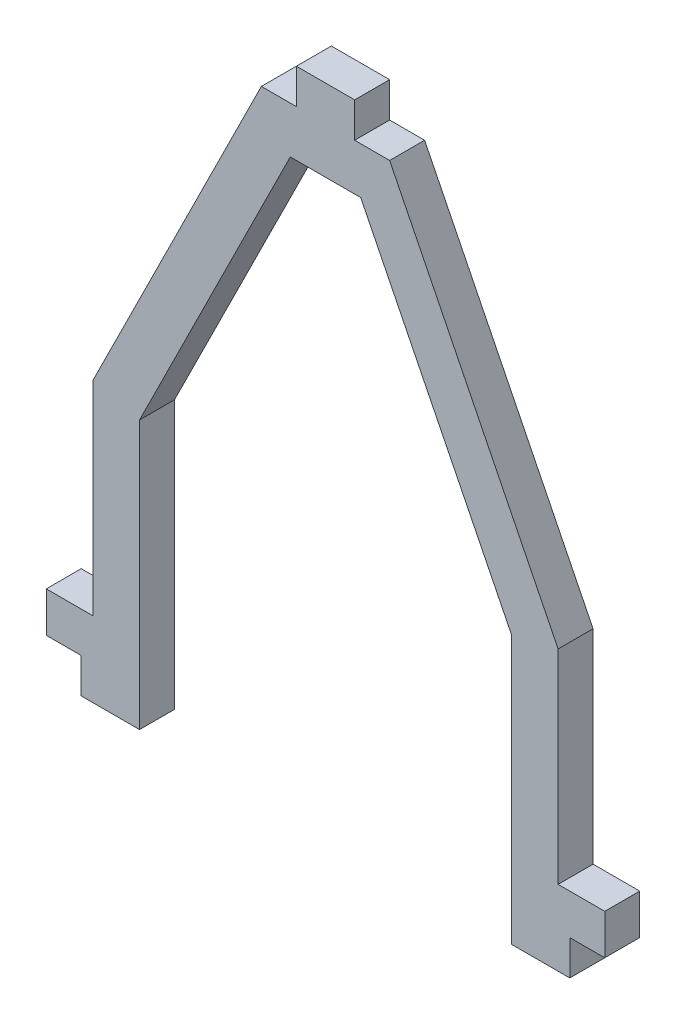
SolidWorks part; units mm, degrees
material "Custom Plastic"
ref_plane "Front Plane" through (0, 0, 0) normal (0, 0, 1) x (1, 0, 0)
ref_plane "Top Plane" through (0, 0, 0) normal (0, 1, 0) x (1, 0, 0)
ref_plane "Right Plane" through (0, 0, 0) normal (1, 0, 0) x (0, 0, -1)
sketch "Sketch1" plane through (0, 0, 0) normal (0, 0, 1) x (1, 0, 0)
  line L20 (-6.3839, -51.0934) -> (-6.3839, -28.0934)
  line L38 (-6.3839, -28.0934) -> (6.5444, -2.0934)
  line L39 (6.5444, -2.0934) -> (12.5879, -2.0934)
  line L40 (9.5661, -2.0934) -> (9.5661, 4.9066) construction
  line L41 (7.0661, 4.9066) -> (12.0661, 4.9066)
  line L42 (12.0661, 4.9066) -> (12.0661, 1.9066)
  line L44 (4.0661, 1.9066) -> (-10.3839, -27.1538)
  line L45 (-10.3839, -27.1538) -> (-10.3839, -44.6388)
  line L46 (-10.3839, -44.6388) -> (-14.3839, -44.6388)
  line L47 (-14.3839, -44.6388) -> (-14.3839, -48.0934)
  line L48 (-14.3839, -48.0934) -> (-11.3839, -48.0934)
  line L49 (-11.3839, -48.0934) -> (-11.3839, -51.0934)
  line L50 (-11.3839, -51.0934) -> (-6.3839, -51.0934)
  line L51 (-10.3839, -27.1538) -> (-6.3839, -28.0934) construction
  line L52 (4.0661, 1.9066) -> (6.5444, -2.0934) construction
  line L53 (15.0661, 1.9066) -> (12.5879, -2.0934) construction
  line L54 (29.5161, -27.1538) -> (25.5161, -28.0934) construction
  line L55 (30.5161, -51.0934) -> (25.5161, -51.0934)
  line L56 (30.5161, -48.0934) -> (30.5161, -51.0934)
  line L57 (33.5161, -48.0934) -> (30.5161, -48.0934)
  line L58 (33.5161, -44.6388) -> (33.5161, -48.0934)
  line L59 (29.5161, -44.6388) -> (33.5161, -44.6388)
  line L60 (29.5161, -27.1538) -> (29.5161, -44.6388)
  line L61 (15.0661, 1.9066) -> (29.5161, -27.1538)
  line L63 (7.0661, 4.9066) -> (7.0661, 1.9066)
  line L64 (25.5161, -28.0934) -> (12.5879, -2.0934)
  line L65 (25.5161, -51.0934) -> (25.5161, -28.0934)
  line L66 (4.0661, 1.9066) -> (7.0661, 1.9066)
  line L67 (12.0661, 1.9066) -> (15.0661, 1.9066)
  point P28 (7.0661, 3.4066)
  dimension "D1" = 3
  dimension "D2" = 3
  dimension "D3" = 4
  dimension "D4" = 5
  dimension "D5" = 4
  dimension "D6" = 50
  dimension "D7" = 41.9
  dimension "D8" = 20
  dimension "D9" = 4
  dimension "D10" = 5
  dimension "D11" = 3
  dimension "D12" = 3
extrude "Boss-Extrude1" add sketch "Sketch1" along normal blind 3
